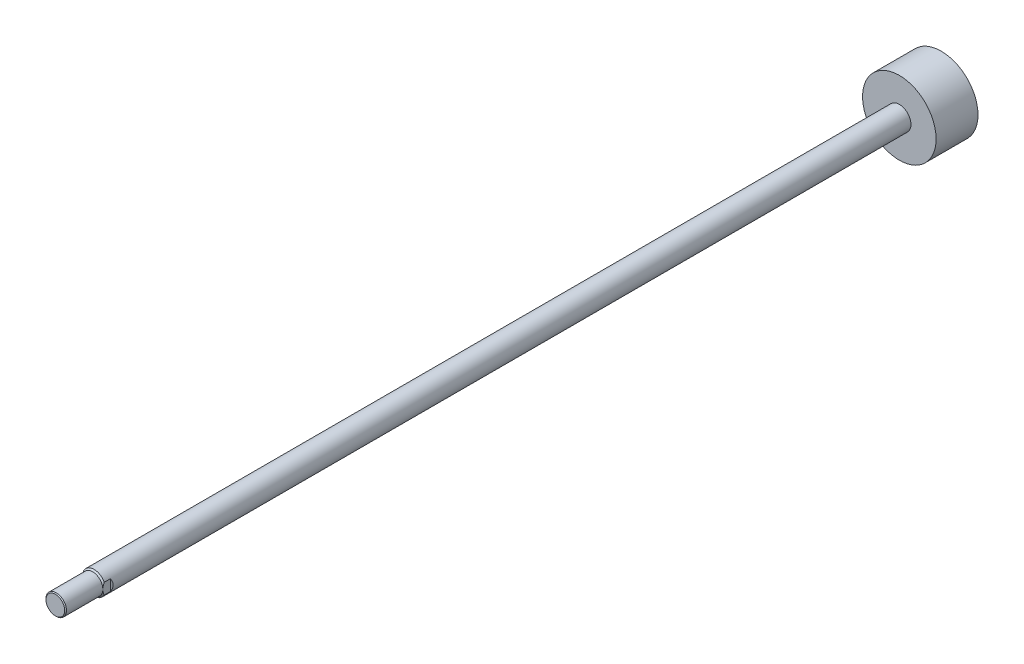
SolidWorks part; units mm, degrees
material "A3钢"
ref_plane "前视基准面" through (0, 0, 0) normal (0, 0, 1) x (1, 0, 0)
ref_plane "上视基准面" through (0, 0, 0) normal (0, 1, 0) x (1, 0, 0)
ref_plane "右视基准面" through (0, 0, 0) normal (1, 0, 0) x (0, 0, -1)
sketch "草图1" plane through (0, 0, 0) normal (1, 0, 0) x (0, 0, -1)
  line L0 (-52, 0) -> (-52, 10.08)
  line L1 (-52, 10.08) -> (-51.08, 11)
  line L2 (-51.08, 11) -> (-12, 11)
  line L3 (-12, 11) -> (-10.5, 12.5)
  line L4 (-10.5, 12.5) -> (854.5, 12.5)
  line L5 (854.5, 12.5) -> (854.5, 39.5)
  line L6 (854.5, 39.5) -> (899.5, 39.5)
  line L7 (899.5, 39.5) -> (899.5, 0)
  line L8 (899.5, 0) -> (-52, 0)
  line L9 (899.5, 0) -> (-52, 0) construction
revolve "旋转1" add sketch "草图1" angle 360 about L9 reverse direction yes
cosmetic thread "装饰螺纹线1" parameters "D1"=36, "D2"=20.16
sketch "草图2" plane through (0, 0, 0) normal (0, 1, 0) x (1, 0, 0)
  line L0 (11, -3.9) -> (11, -12)
  line L1 (11, -12) -> (12.5, -12)
  line L2 (12.5, -12) -> (12.5, -2.4)
  line L3 (12.5, -2.4) -> (11, -3.9)
extrude "切除-拉伸1" cut sketch "草图2" along normal blind 12.5 and the other way blind 12.5
sketch "草图3" plane through (0, 0, 0) normal (0, 1, 0) x (1, 0, 0)
  line L0 (-12.5, -2.4) -> (-12.5, -12)
  line L1 (-12.5, -12) -> (-11, -12)
  line L2 (-11, -12) -> (-11, -3.9)
  line L3 (-11, -3.9) -> (-12.5, -2.4)
extrude "切除-拉伸2" cut sketch "草图3" along normal blind 12.5 and the other way blind 12.5
ref_plane "基准面1" through (0, 0, -20) normal (0, 0, 1) x (1, 0, 0)
ref_plane "基准面2" through (0, 0, 32) normal (0, 0, 1) x (1, 0, 0)
ref_plane "基准面3" through (0, 0, -1786) normal (0, 0, 1) x (1, 0, 0)
ref_plane "基准面4" through (0, 0, -1728) normal (0, 0, 1) x (1, 0, 0)
ref_plane "基准面5" through (0, 0, -1733) normal (0, 0, 1) x (1, 0, 0)
ref_plane "IP1_POLE XY" through (0, 0, -20) normal (0, 0, -1) x (-1, 0, 0)
ref_plane "IP1_POLE XZ" through (0, 0, 0) normal (0, 1, 0) x (1, 0, 0)
ref_plane "IP1_POLE YZ" through (0, 0, 0) normal (1, 0, 0) x (0, 0, -1)
ref_axis "IP1_POLE X" through (-80.9, 0, -20) along (1, 0, 0)
ref_axis "IP1_POLE Y" through (0, 50, -20) along (0, -1, 0)
ref_axis "IP1_POLE Z" through (0, 0, -80.9) along (0, 0, 1)
sketch3d "IP1_POLE"
  point P0 (0, 0, -20)
ref_plane "IP_A_NUT XY" through (0, 0, -1728) normal (0, 0, -1) x (-1, 0, 0)
ref_plane "IP_A_NUT XZ" through (0, 0, 0) normal (0, 1, 0) x (1, 0, 0)
ref_plane "IP_A_NUT YZ" through (0, 0, 0) normal (1, 0, 0) x (0, 0, -1)
ref_axis "IP_A_NUT X" through (-80.9, 0, -1728) along (1, 0, 0)
ref_axis "IP_A_NUT Y" through (0, 50, -1728) along (0, -1, 0)
ref_axis "IP_A_NUT Z" through (0, 0, -80.9) along (0, 0, 1)
sketch3d "IP_A_NUT"
  point P0 (0, 0, -1728)
ref_plane "IP_NUT XY" through (0, 0, 32) normal (0, 0, 1) x (1, 0, 0)
ref_plane "IP_NUT XZ" through (0, 0, 0) normal (0, -1, 0) x (-1, 0, 0)
ref_plane "IP_NUT YZ" through (0, 0, 0) normal (1, 0, 0) x (0, 0, -1)
ref_axis "IP_NUT X" through (-80.9, 0, 32) along (1, 0, 0)
ref_axis "IP_NUT Y" through (0, -50, 32) along (0, 1, 0)
ref_axis "IP_NUT Z" through (0, 0, 80.9) along (0, 0, -1)
sketch3d "IP_NUT"
  point P0 (0, 0, 32)
ref_plane "IP_NUT_2 XY" through (0, 0, -1786) normal (0, 0, -1) x (-1, 0, 0)
ref_plane "IP_NUT_2 XZ" through (0, 0, 0) normal (0, 1, 0) x (1, 0, 0)
ref_plane "IP_NUT_2 YZ" through (0, 0, 0) normal (1, 0, 0) x (0, 0, -1)
ref_axis "IP_NUT_2 X" through (-80.9, 0, -1786) along (1, 0, 0)
ref_axis "IP_NUT_2 Y" through (0, 50, -1786) along (0, -1, 0)
ref_axis "IP_NUT_2 Z" through (0, 0, -80.9) along (0, 0, 1)
sketch3d "IP_NUT_2"
  point P0 (0, 0, -1786)
ref_plane "IP_NUT_A_2 XY" through (0, 0, -1733) normal (0, 0, -1) x (-1, 0, 0)
ref_plane "IP_NUT_A_2 XZ" through (0, 0, 0) normal (0, 1, 0) x (1, 0, 0)
ref_plane "IP_NUT_A_2 YZ" through (0, 0, 0) normal (1, 0, 0) x (0, 0, -1)
ref_axis "IP_NUT_A_2 X" through (-80.9, 0, -1733) along (1, 0, 0)
ref_axis "IP_NUT_A_2 Y" through (0, 50, -1733) along (0, -1, 0)
ref_axis "IP_NUT_A_2 Z" through (0, 0, -80.9) along (0, 0, 1)
sketch3d "IP_NUT_A_2"
  point P0 (0, 0, -1733)
